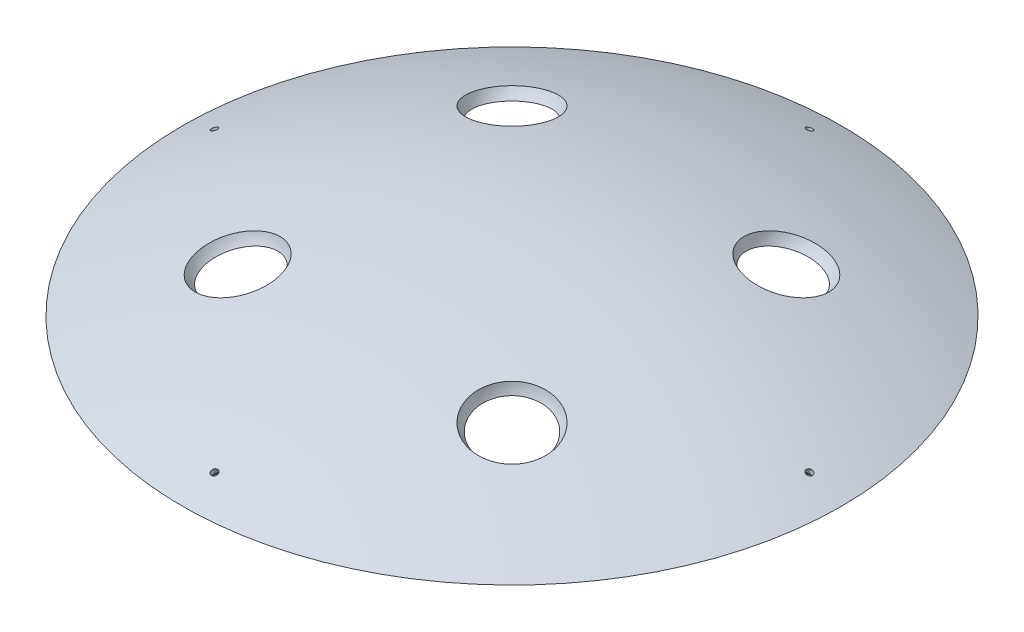
SolidWorks part; units mm, degrees
ref_plane "Front Plane" through (0, 0, 0) normal (0, 0, 1) x (1, 0, 0)
ref_plane "Top Plane" through (0, 0, 0) normal (0, 1, 0) x (1, 0, 0)
ref_plane "Right Plane" through (0, 0, 0) normal (1, 0, 0) x (0, 0, -1)
sketch "Sketch1" plane through (0, 0, 0) normal (0, 0, 1) x (1, 0, 0)
  line L0 (-150, 394.9445) -> (-150, 372.9445)
  line L1 (-150, 372.9445) -> (-100.1531, 349.7005)
  line L2 (0, 394.9445) -> (0, 544.9445)
  line L3 (0, 394.9445) -> (0, 370.6385)
  line L4 (-141.8706, 372.4638) -> (-96.4504, 351.284)
  line L9 (-100.1531, 349.7005) -> (-96.4504, 348.0288)
  line L10 (0, 370.6385) -> (0, 367.6385)
  line L12 (3, 394.9445) -> (3, 367.6203) construction
  line L13 (-153, 371.0333) -> (-100.1883, 346.4068) construction
  line L14 (-153, 394.9445) -> (-153, 371.0333) construction
  line L15 (3, 394.9445) -> (3, 547.9151) construction
  arc A0 (0, 370.6385) -> (-100.1531, 349.7005) centre (0, 120.6385) ccw
  arc A1 (0, 544.9445) -> (-150, 394.9445) centre (0, 394.9445) ccw
  arc A2 (0, 367.6385) -> (-96.4504, 348.0288) centre (0, 120.6385) ccw
  arc A4 (3, 367.6203) -> (-100.1883, 346.4068) centre (0, 120.6385) ccw construction
  arc A5 (3, 547.9151) -> (-153, 394.9445) centre (0, 394.9445) ccw construction
  dimension "D1" = 500
  dimension "D2" = 300
  dimension "D3" = 22
  dimension "D4" = 55
  dimension "D5" = 115
  dimension "D6" = 3
  dimension "D7" = 3
revolve "Revolve1" add sketch "Sketch1" angle 360 about L2 region at (-97.9012, 349.5557, 0)
sketch "Sketch3" plane through (0, 0, 0) normal (0, 0, 1) x (1, 0, 0)
  line L0 (-150, 372.9445) -> (-100.1531, 349.7005)
  line L1 (-150, 372.9445) -> (-150, 394.9445)
  line L2 (-147, 374.8557) -> (-147, 394.9445)
  line L3 (-147, 374.8557) -> (-98.8852, 352.4194)
  line L4 (-98.8852, 352.4194) -> (-96.4504, 351.284)
  line L5 (0, 120.6385) -> (-90.3797, 353.7297)
  line L6 (0.9324, 121.0001) -> (-89.4474, 354.0913)
  line L7 (1.8647, 121.3616) -> (-88.515, 354.4528)
  circle A0 centre (0, 120.6385) radius 250
  arc A1 (100.1531, 349.7005) -> (-100.1531, 349.7005) centre (0, 120.6385) ccw construction
  arc A2 (-135.5683, 330.6891) -> (-150, 394.8277) centre (0, 394.8861) ccw
  circle A3 centre (0, 120.6385) radius 247
  circle A4 centre (0.9324, 121.0001) radius 248.5
  dimension "D1" = 500
  dimension "D2" = 300
  dimension "D10" = 497
  dimension "D3" = 22
  dimension "D4" = 55
  dimension "D5" = 115
  dimension "D7" = 1.5
  dimension "D11" = 1
  dimension "D6" = 3
  dimension "D8" = 1
  dimension "D9" = 3
revolve "Cut-Revolve1" cut sketch "Sketch3" angle 360 about L5 region at (-89.6424, 353.2105, 0) region at (-89.0997, 351.8121, 0) region at (-88.1666, 352.1718, 0)
sketch "Sketch4" plane through (0, 0, 0) normal (0, 0, 1) x (1, 0, 0)
  line L0 (0, 0) -> (0, 436.9518)
pattern_circular "CirPattern2" count 4 every 90 about axis through (0, 0, 0) along (0, 1, 0) of "Cut-Revolve1"
ref_plane "Plane1" through (0, 0, 0) normal (0.7071, 0, 0.7071) x (0, 1, 0)
sketch "Sketch5" plane through (0, 0, 0) normal (0.7071, 0, 0.7071) x (0, 1, 0)
  line L0 (0, 0) -> (436.9518, 0) construction
  line L1 (354.9885, 60) -> (388.4674, 60)
  line L2 (354.9885, 60) -> (309.9583, 60)
  arc A0 (360.5517, 70.2969) -> (366.0953, 47.4445) centre (120.6385, 0) ccw
  arc A1 (349.7005, -100.1531) -> (349.7005, 100.1531) centre (120.6385, 0) ccw construction
  arc A3 (354.9885, 60) -> (380.2885, 60) centre (367.6385, 60) ccw
  point P7 (370.6385, 0)
  dimension "D1" = 500
  dimension "D2" = 25.3
  dimension "D3" = 60
  dimension "D4" = 3
revolve "Cut-Revolve5" cut sketch "Sketch5" angle 360 about L2 region at (-38.6301, 367.6385, 38.6301)
pattern_circular "CirPattern3" count 4 every 90 about axis through (0, 0, 0) along (0, 1, 0) of "Cut-Revolve5"
